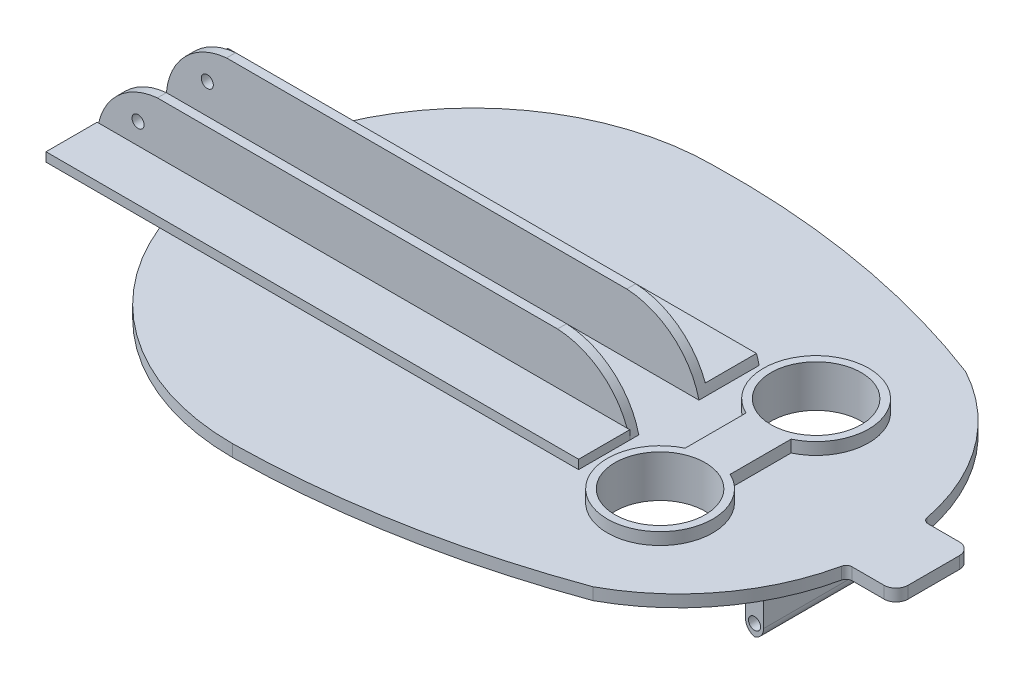
SolidWorks part; units mm, degrees
ref_plane "Front Plane" through (0, 0, 0) normal (0, 0, 1) x (1, 0, 0)
ref_plane "Top Plane" through (0, 0, 0) normal (0, 1, 0) x (1, 0, 0)
ref_plane "Right Plane" through (0, 0, 0) normal (1, 0, 0) x (0, 0, -1)
sketch "Sketch1" plane through (0, 0, 0) normal (0, 1, 0) x (1, 0, 0)
  line L0 (-77.1692, 0) -> (142.8308, 0) construction
  line L8 (110.6578, 12.5) -> (121, 12.5)
  line L9 (125, 8.5) -> (125, -8.5)
  line L10 (121, -12.5) -> (110.4018, -12.5)
  arc A0 (-28.0734, 80) -> (-28.0734, -80) centre (-28.0734, 0) ccw
  arc A1 (-28.0734, -80) -> (73.0718, -61.2945) centre (-32.8847, 228.827) ccw
  arc A2 (-28.0734, 80) -> (73.0718, 62.5462) centre (-21.614, -184.3645) cw
  arc A3 (73.0718, 62.5462) -> (108.6949, 14.1166) centre (39.6226, 0.6259) cw
  arc A4 (108.446, -14.082) -> (73.0718, -61.2945) centre (39.6226, 0.6259) cw
  arc A5 (125, -8.5) -> (121, -12.5) centre (121, -8.5) cw
  arc A6 (121, 12.5) -> (125, 8.5) centre (121, 8.5) cw
  arc A7 (110.4018, -12.5) -> (108.446, -14.082) centre (110.4018, -14.5) ccw
  arc A8 (110.6578, 12.5) -> (108.6949, 14.1166) centre (110.6578, 14.5) cw
  point P3 (0, 0)
  point P22 (108.7651, -12.5)
  dimension "D4" = 4
  dimension "D6" = 2
  dimension "D1" = 220
  dimension "D2" = 25
  dimension "D3" = 160
  dimension "D5" = 12.5
extrude "Boss-Extrude1" add sketch "Sketch1" along normal blind 4
sketch "Sketch2" plane through (0, 4, 0) normal (0, 1, 0) x (1, 0, 0)
  line L0 (60, 80.9744) -> (60, -104.3003) construction
  line L1 (125, -8.5) -> (125, 8.5) construction
  line L2 (125, 0) -> (-12.3095, 0) construction
  line L4 (67.5, 10.1152) -> (67.5, -10.1152)
  line L5 (52.5, 10.1152) -> (52.5, -10.1152)
  arc A0 (67.5, 10.1152) -> (52.5, 10.1152) centre (60, 25.9266) ccw
  arc A1 (52.5, -10.1152) -> (67.5, -10.1152) centre (60, -25.9266) ccw
  circle A2 centre (60, 25.9266) radius 15
  circle A3 centre (60, -25.9266) radius 15
  dimension "D2" = 35
  dimension "D3" = 35
  dimension "D4" = 30
  dimension "D5" = 30
  dimension "D1" = 65
  dimension "D7" = 7.5
extrude "Boss-Extrude2" add sketch "Sketch2" along normal blind 4 and the other way blind 10
sketch "Sketch3" plane through (0, 4, 0) normal (0, 1, 0) x (1, 0, 0)
  circle A0 centre (60, 25.9266) radius 15
  circle A1 centre (60, -25.9266) radius 15
extrude "Cut-Extrude1" cut sketch "Sketch3" against normal blind 40
sketch "Sketch4" plane through (0, 0, 0) normal (0, -1, 0) x (1, 0, 0)
  line L0 (125, 0) -> (76.1875, 0) construction
  line L1 (125, 8.5) -> (125, -8.5) construction
  line L3 (91, 25) -> (91, -25) construction
  line L4 (87.4613, -25) -> (93.4613, -25)
  line L5 (87.4613, -25) -> (87.4613, 25)
  line L6 (87.4613, 25) -> (93.4613, 25)
  line L7 (93.4613, -25) -> (93.4613, 25)
  line L8 (87.4613, -25) -> (93.4613, 25) construction
  line L9 (87.4613, 25) -> (93.4613, -25) construction
  point P6 (90.4613, 0)
  dimension "D1" = 50
  dimension "D2" = 25
  dimension "D3" = 6
  dimension "D4" = 34
extrude "Boss-Extrude3" add sketch "Sketch4" along normal blind 20
sketch "Sketch5" plane through (0, 0, 25) normal (0, 0, 1) x (1, 0, 0)
  line L0 (93.4613, -20) -> (87.4613, -20) construction
  circle A0 centre (90.4613, -16) radius 2
  dimension "D1" = 4
  dimension "D2" = 4
extrude "Cut-Extrude2" cut sketch "Sketch5" against normal blind 59
fillet "Fillet1" radius 4 2 edges at (87.4613, -20, 0) (93.4613, -20, 0)
ref_plane "Plane1" through (-140, 0, 0) normal (1, 0, 0) x (0, 0, -1)
sketch "Sketch6" plane through (-140, 0, 0) normal (1, 0, 0) x (0, 0, -1)
  line L0 (0, 0) -> (0, 50.9595) construction
  line L1 (-10, 24.0149) -> (-10, 4.0149)
  line L2 (-30, 4.0149) -> (-30, 7.0149)
  line L3 (-30, 7.0149) -> (-13, 7.0149)
  line L4 (-13, 7.0149) -> (-13, 24.0149)
  line L5 (-13, 24.0149) -> (-10, 24.0149)
  line L7 (-10, 4.0149) -> (-30, 4.0149)
  line L8 (10, 4.0149) -> (30, 4.0149)
  line L9 (13, 24.0149) -> (10, 24.0149)
  line L10 (13, 7.0149) -> (13, 24.0149)
  line L11 (30, 7.0149) -> (13, 7.0149)
  line L12 (30, 4.0149) -> (30, 7.0149)
  line L13 (10, 24.0149) -> (10, 4.0149)
  dimension "D1" = 20
  dimension "D2" = 3
  dimension "D3" = 3
  dimension "D4" = 20
  dimension "D5" = 10
extrude "Boss-Extrude4" add sketch "Sketch6" along normal blind 177 separate body
sketch "Sketch7" plane through (0, 0, 13) normal (0, 0, 1) x (1, 0, 0)
  line L0 (37, 24.0149) -> (-140, 24.0149) construction
  line L1 (-140, 4.0149) -> (-157.2046, 4.0149)
  line L2 (-157.2046, 4.0149) -> (-157.2046, 69.6636)
  line L3 (-157.2046, 69.6636) -> (45.1511, 69.6636)
  line L4 (45.1511, 69.6636) -> (37, 4.0149)
  line L5 (-116.0976, 24.0149) -> (-96.9402, 49.7598)
  line L6 (-96.9402, 49.7598) -> (10.4797, 49.7598)
  line L7 (10.4797, 49.7598) -> (10.4797, 24.0149)
  arc A0 (-140, 4.0149) -> (-116.0976, 24.0149) centre (-118.0488, 2.0637) cw
  arc A1 (37, 4.0149) -> (10.4797, 24.0149) centre (11.7383, -1.8994) ccw
extrude "Cut-Extrude3" cut sketch "Sketch7" against normal blind 48
sketch "Sketch8" plane through (0, 0, 13) normal (0, 0, 1) x (1, 0, 0)
  line L0 (12.9969, 24.0149) -> (-120, 24.0149) construction
  circle A0 centre (-126.3982, 14.0149) radius 2
  dimension "D1" = 4
  dimension "D2" = 10
extrude "Cut-Extrude4" cut sketch "Sketch8" against normal blind 48
